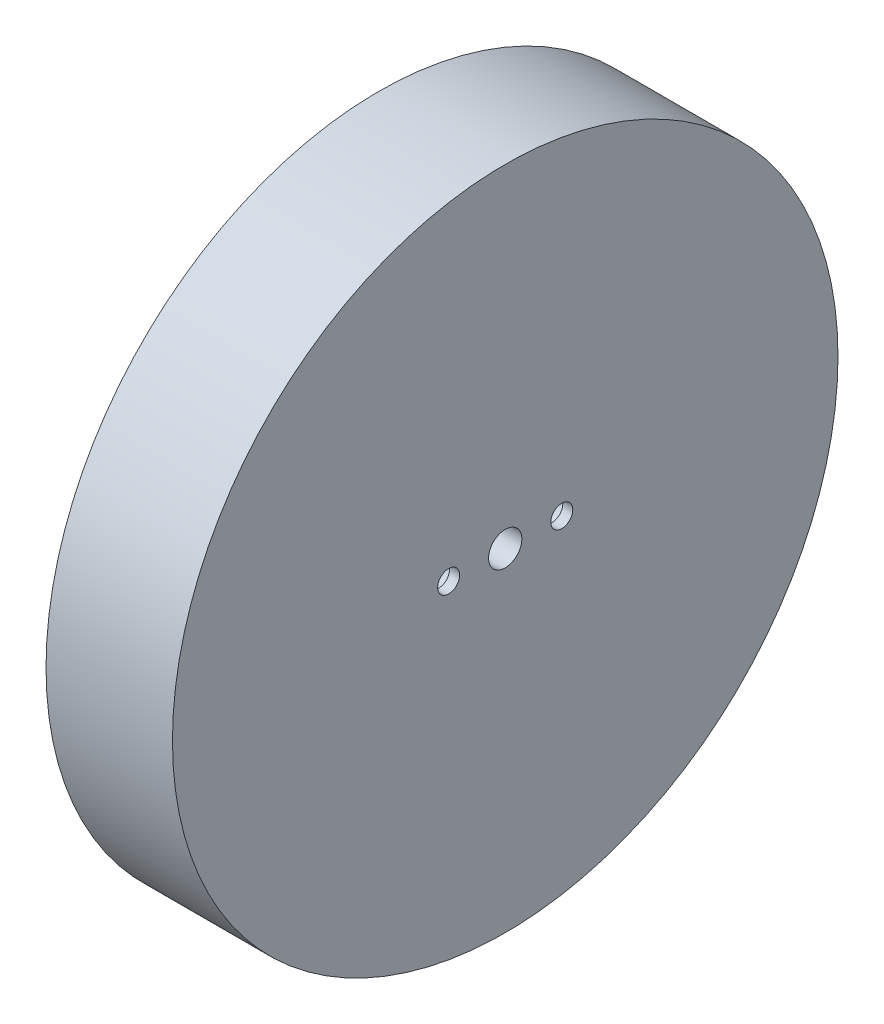
SolidWorks part; units mm, degrees
ref_plane "Plane1" through (0, 0, 0) normal (0, 0, 1) x (1, 0, 0)
ref_plane "Plane2" through (0, 0, 0) normal (0, 1, 0) x (1, 0, 0)
ref_plane "Plane3" through (0, 0, 0) normal (1, 0, 0) x (0, 0, -1)
sketch "HoldingSke" plane through (0, 0, 0) normal (0, 1, 0) x (1, 0, 0)
  line L0 (0, 0) -> (0.0872, -0.9962)
  line L1 (-15, 0) -> (100, 0) construction
  line L2 (0, 0) -> (-2.1039, 2.3779)
  line L3 (0, 0) -> (-11.863, 4.5341)
  line L4 (0, 0) -> (0.7527, 8.6031)
  line L5 (0, 0) -> (-23.7986, -8.8762)
  line L6 (0, 0) -> (-10.5278, -7.1032)
  line L7 (-2.1039, 2.3779) -> (3.3635, 27.1825)
  line L8 (-76.2, 3.3779) -> (-54.61, 3.3779)
  line L9 (-71.009, 38.7566) -> (-53.1078, 45.2721)
  line L10 (-76.2, 71.12) -> (104.1128, 71.12)
  line L11 (0, 0) -> (-15, 0)
  line L12 (-76.2, 101.6) -> (-76.162, 101.6)
  line L13 (24.9733, 27.94) -> (52.9518, 28.4284)
  line L14 (24.9733, 27.94) -> (24.9743, 27.94)
  line L15 (24.9733, 27.94) -> (100.4006, 29.5858)
  circle A0 centre (0, 0) radius 50
  circle A1 centre (0, 0) radius 12.7
  circle A2 centre (0, 0) radius 12.7
  dimension "Num_teeth" = 85
  dimension "Pitch_radius" = 180.3128
  dimension "Width" = 15
  dimension "Diameter" = 100
sketch "BasProSke" plane through (0, 0, 0) normal (0, 1, 0) x (1, 0, 0)
  line L0 (-10, 0) -> (60, 0) construction
  line L1 (0, 41.5) -> (0, 50)
  line L2 (0, 41.5) -> (15, 41.5)
  line L3 (15, 41.5) -> (15, 50)
  line L4 (15, 50) -> (0, 50)
  dimension "Thickness" = 15
  dimension "Diameter" = 100
revolve "Base-Revolve" add sketch "BasProSke" angle 360 about L0
sketch "TooCutSke" plane through (0, 0, 0) normal (1, 0, 0) x (0, 0, -1)
  line L3 (0.8804, 42.4909) -> (0.8804, 53.6633) construction
  line L4 (0, 0) -> (0, 59.563) construction
  line L5 (0, 0) -> (-2.5248, 68.2808) construction
  line L6 (-19.1021, 35.2615) -> (36.4888, 37.317) construction
  circle A0 centre (0, 0) radius 42.5 construction
  circle A1 centre (0, 0) radius 43.751 construction
  circle A2 centre (0, 0) radius 35.9432 construction
  circle A3 centre (0, 0) radius 41.4746 construction
  arc A4 (1.2248, 41.4565) -> (0.3791, 43.7494) centre (-19.1021, 35.2615) ccw
  arc A5 (1.2248, 41.4565) -> (-1.2248, 41.4565) centre (0, 0) ccw
  arc A6 (0.3791, 43.7494) -> (-0.3791, 43.7494) centre (0, 0) ccw
  arc A7 (-0.3791, 43.7494) -> (-1.2248, 41.4565) centre (19.1021, 35.2615) ccw
extrude "ToothCut" cut sketch "TooCutSke" along normal through all
fillet "Breaks" [suppressed] radius 0.1
fillet "RootFillets" [suppressed] radius 0.251
pattern_circular "TeethCuts" count 85 every 4.235 about axis through (-10, 0, 0) along (1, 0, 0) of "RootFillets", "Breaks", "ToothCut"
sketch "Sketch1" plane through (15, 0, 0) normal (1, 0, 0) x (0, 0, -1)
  circle A0 centre (0, 0) radius 50
extrude "Boss-Extrude1" add sketch "Sketch1" along normal blind 4
sketch "Sketch2" plane through (19, 0, 0) normal (1, 0, 0) x (0, 0, -1)
  circle A0 centre (0, 0) radius 2.5
  dimension "D1" = 5
extrude "Cut-Extrude1" cut sketch "Sketch2" against normal blind 4
sketch "Sketch3" plane through (19, 0, 0) normal (1, 0, 0) x (0, 0, -1)
  line L0 (0, 0) -> (-8.5, 0) construction
  line L1 (0, 0) -> (8.5, 0) construction
  circle A0 centre (-8.5, 0) radius 1.65
  circle A1 centre (8.5, 0) radius 1.65
  dimension "D2" = 3.3
  dimension "D1" = 8.5
extrude "Cut-Extrude2" cut sketch "Sketch3" against normal blind 4
sketch "Sketch4" plane through (15, 0, 0) normal (-1, 0, 0) x (0, 0, 1)
  circle A0 centre (-8.5, 0) radius 2.75
  circle A1 centre (8.5, 0) radius 2.75
  dimension "D1" = 5.5
extrude "Cut-Extrude3" cut sketch "Sketch4" against normal blind 2.5
equation "' \"Module@HoldingSke\" = 6.35"
equation "' \"Num_teeth@HoldingSke\" = 24"
equation "' \"Ap@HoldingSke\" =  14.5"
equation "' \"Ap@HoldingSke\" = 14.5"
equation "' \"Width@HoldingSke\" = 12"
equation "' \"Diameter@HoldingSke\" = 8 * 25.4"
equation "' \"Show_teeth@HoldingSke\" = 100"
equation "' \"Backlash@HoldingSke\" = 0.009 * 25.4"
equation "' \"Addendum_fac@HoldingSke\" = 1.0"
equation "' \"Dedendum_fac@HoldingSke\" = 1.25"
equation "' \"Dedendum_add@HoldingSke\" = 0.00005 * 25.4"
equation "' \"Clearance_fac@HoldingSke\" = 0.25"
equation "\"Pitch@HoldingSke\" = 1 / \"Module@HoldingSke\" "
equation "\"Overcut_dia@TooCutSke\" = (\"Num_teeth@HoldingSke\" - 2 * \"Addendum_fac@HoldingSke\") / \"Pitch@HoldingSke\" - 0.002 * 25.4"
equation "\"Pitch_dia@TooCutSke\" = \"Num_teeth@HoldingSke\" / \"Pitch@HoldingSke\""
equation "\"Base_dia@TooCutSke\" = \"Num_teeth@HoldingSke\" / \"Pitch@HoldingSke\" * cos((\"Ap@HoldingSke\"  * 3.14159265 / 180)) * 0.90"
equation "\"Root_dia@TooCutSke\" = \"Num_teeth@HoldingSke\"  / \"Pitch@HoldingSke\" + 2 *  \"Dedendum_fac@HoldingSke\"/ \"Pitch@HoldingSke\" + \"Dedendum_add@HoldingSke\" * 2"
equation "\"Half_ang@TooCutSke\" = 180 / \"Num_teeth@HoldingSke\""
equation "\"Half_CT@TooCutSke\" = \"Num_teeth@HoldingSke\" / \"Pitch@HoldingSke\" * sin((3.14159265 / 2 / \"Num_teeth@HoldingSke\")) / 2 + 10 * \"Backlash@HoldingSke\" / 4"
equation "\"Flank_rad@TooCutSke\" = \"Num_teeth@HoldingSke\" / \"Pitch@HoldingSke\" / 4"
equation "\"Radius@RootFillets\"= \"Clearance_fac@HoldingSke\" / \"Pitch@HoldingSke\" + \"Dedendum_add@HoldingSke\""
equation "\"Break_rad@Breaks\" = 0.02 / \"Pitch@HoldingSke\" * 5"
equation "\"Num_teeth@TeethCuts\" = int( \"Show_teeth@HoldingSke\" ) + 1"
equation "\"Num_teeth@TeethCuts\" = ((sgn( \"Num_teeth@TeethCuts\" - \"Num_teeth@HoldingSke\" )-1)*( \"Num_teeth@TeethCuts\" - \"Num_teeth@HoldingSke\" ))/-2+ \"Num_teeth@HoldingSke\""
equation "\"Num_teeth@TeethCuts\" = ((sgn( \"Num_teeth@TeethCuts\" - 2.0)+1)*( \"Num_teeth@TeethCuts\" - 2.0))/2 +2.0"
equation "\"Angle@TeethCuts\" = 360.0 / \"Num_teeth@HoldingSke\""
equation "\"Diameter@BasProSke\" = \"Num_teeth@HoldingSke\"  / \"Pitch@HoldingSke\" + 2 *  \"Dedendum_fac@HoldingSke\"/ \"Pitch@HoldingSke\" + \"Dedendum_add@HoldingSke\" * 2 + 0.002 * 25.4"
equation "\"Diameter@BasProSke\" = ((sgn( \"Diameter@BasProSke\"  - \"Diameter@HoldingSke\" )+1)*( \"Diameter@BasProSke\"  - \"Diameter@HoldingSke\" ))/2 + \"Diameter@HoldingSke\""
equation "\"Inside_diameter@BasProSke\" =  (\"Num_teeth@HoldingSke\" - 2 * \"Addendum_fac@HoldingSke\") / \"Pitch@HoldingSke\" "
equation "\"Thickness@BasProSke\"  = \"Width@HoldingSke\""
